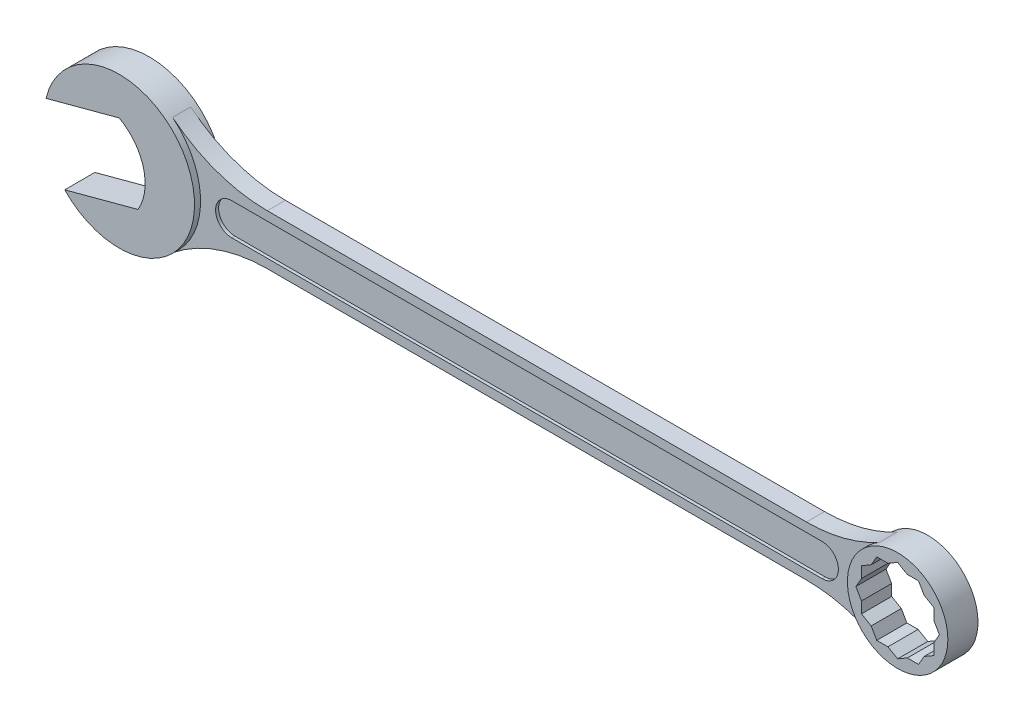
SolidWorks part; units mm, degrees
material "AISI 304"
ref_plane "Front Plane" through (0, 0, 0) normal (0, 0, 1) x (1, 0, 0)
ref_plane "Top Plane" through (0, 0, 0) normal (0, 1, 0) x (1, 0, 0)
ref_plane "Right Plane" through (0, 0, 0) normal (1, 0, 0) x (0, 0, -1)
sketch "Sketch1" plane through (0, 0, 0) normal (0, 0, 1) x (1, 0, 0)
  line L0 (-66.6174, 0) -> (294.8495, 0) construction
  line L1 (0, 54.5023) -> (0, -95.6284) construction
  line L2 (-24.2902, 5.9148) -> (0.0169, 12.4278)
  line L3 (-18.0786, -17.2675) -> (6.2286, -10.7544)
  line L4 (35.3333, 0) -> (231.3333, 0) construction
  line L5 (35.3333, 5.3333) -> (231.3333, 5.3333)
  line L6 (35.3333, -5.3333) -> (231.3333, -5.3333)
  line L7 (47.1405, 8.3333) -> (226.0585, 8.3333)
  line L8 (47.1405, -8.3333) -> (226.0585, -8.3333)
  line L9 (0, 0) -> (-29.3124, -7.8542) construction
  line L10 (-24.2902, 5.9148) -> (-21.1844, -5.6763) construction
  line L11 (-18.0786, -17.2675) -> (-21.1844, -5.6763) construction
  line L12 (0, 0) -> (8.0494, 2.1568) construction
  line L13 (258.3333, 19.271) -> (258.3333, -18.8318) construction
  line L26 (255.1179, 12) -> (251.4051, 12)
  line L27 (270.3333, -6.9282) -> (270.3333, -3.2154)
  line L28 (270.3333, 6.9282) -> (267.1179, 8.7846)
  line L29 (258.3333, 13.8564) -> (255.1179, 12)
  line L30 (246.3333, 6.9282) -> (246.3333, 3.2154)
  line L31 (246.3333, -6.9282) -> (249.5487, -8.7846)
  line L32 (258.3333, -13.8564) -> (261.5487, -12)
  line L33 (244.4769, 0) -> (246.3333, -3.2154)
  line L34 (251.4051, -12) -> (255.1179, -12)
  line L35 (265.2615, -12) -> (267.1179, -8.7846)
  line L36 (272.1897, 0) -> (270.3333, 3.2154)
  line L37 (265.2615, 12) -> (261.5487, 12)
  line L38 (251.4051, 12) -> (249.5487, 8.7846)
  line L39 (261.5487, 12) -> (258.3333, 13.8564)
  line L40 (267.1179, 8.7846) -> (265.2615, 12)
  line L41 (249.5487, 8.7846) -> (246.3333, 6.9282)
  line L42 (246.3333, 3.2154) -> (244.4769, 0)
  line L43 (246.3333, -3.2154) -> (246.3333, -6.9282)
  line L44 (249.5487, -8.7846) -> (251.4051, -12)
  line L45 (255.1179, -12) -> (258.3333, -13.8564)
  line L46 (261.5487, -12) -> (265.2615, -12)
  line L47 (267.1179, -8.7846) -> (270.3333, -6.9282)
  line L48 (270.3333, -3.2154) -> (272.1897, 0)
  line L49 (270.3333, 3.2154) -> (270.3333, 6.9282)
  arc A0 (-18.0786, -17.2675) -> (-24.2902, 5.9148) centre (0, 0) ccw
  circle A2 centre (258.3333, 0) radius 16.6667
  arc A3 (35.3333, 5.3333) -> (35.3333, -5.3333) centre (35.3333, 0) ccw
  arc A4 (231.3333, -5.3333) -> (231.3333, 5.3333) centre (231.3333, 0) ccw
  arc A5 (226.0585, 8.3333) -> (250.2646, 14.5833) centre (226.0585, 58.3333) ccw
  arc A6 (47.1405, 8.3333) -> (15.7135, 19.4444) centre (47.1405, 58.3333) cw
  arc A7 (226.0585, -8.3333) -> (250.2646, -14.5833) centre (226.0585, -58.3333) cw
  arc A8 (47.1405, -8.3333) -> (15.7135, -19.4444) centre (47.1405, -58.3333) ccw
  arc A9 (0.0169, 12.4278) -> (6.2286, -10.7544) centre (-8.0494, -2.1568) cw
  circle A10 centre (258.3333, 0) radius 12 construction
  circle A11 centre (258.3333, 0) radius 12 construction
  point P14 (133.3333, 0)
  point P31 (24.1481, 6.4705)
  point P38 (200.953, 0)
  dimension "D6" = 33.3333
  dimension "D5" = 16.6667
  dimension "D9" = 50
  dimension "D8" = 50
  dimension "D10" = 50
  dimension "D11" = 50
  dimension "D1" = 300
  dimension "D2" = 24
  dimension "D3" = 15
  dimension "D4" = 25
  dimension "D7" = 16.6667
  dimension "D12" = 3
  dimension "D13" = 3
  dimension "D14" = 16.6667
  dimension "D15" = 5
  dimension "D16" = 5
  dimension "D17" = 24
  dimension "D18" = 24
extrude "Boss-Extrude1" add sketch "Sketch1" along normal mid plane 10 contours L2 A9 L3 A0 | A2 L49 L36 L48 L27 L47 L35 L46 L32 L45 L34 L44 L31 L43 L33 L42 L30 L41 L38 L26 L29 L39 L37 L40 L28 region at (-7.7846, 23.0171, 0) region at (266.5585, 13.9511, 0)
extrude "Boss-Extrude2" add sketch "Sketch1<3>" along normal mid plane 6 contours A8 L8 A7 A2 A5 L7 A6 A0 A4 L6 A3 L5 region at (29.6813, 8.9513, 0)
sketch "Sketch1<3>" plane through (0, 0, 0) normal (0, 0, 1) x (1, 0, 0) same geometry as "Sketch1"
extrude "Boss-Extrude3" add sketch "Sketch1<4>" along normal mid plane 4 contours L6 A4 L5 A3 region at (133.3333, 0, 0)
sketch "Sketch1<4>" plane through (0, 0, 0) normal (0, 0, 1) x (1, 0, 0) same geometry as "Sketch1"
equation "\"C\"= 300"
equation "\"D1@Sketch1\"=\"C\""
equation "\"B\" = 24"
equation "\"D2@Sketch1\"=\"B\""
equation "\"R\" = 25"
equation "\"D9@Sketch1\"=\"R\"*2"
equation "\"D8@Sketch1\"=\"R\"*2"
equation "\"D4@Sketch1\"=\"R\""
equation "\"D5@Sketch1\"=\"R\"*2/3"
equation "\"D7@Sketch1\"=\"R\"*2/3"
equation "\"D11@Sketch1\"=\"R\"*2"
equation "\"D10@Sketch1\"=\"R\"*2"
equation "\"D17@Sketch1\"=\"B\""
equation "\"D18@Sketch1\"=\"B\""
equation "\"D6@Sketch1\"=\"R\"*4/3"
equation "\"D14@Sketch1\"=\"R\"*2/3"
